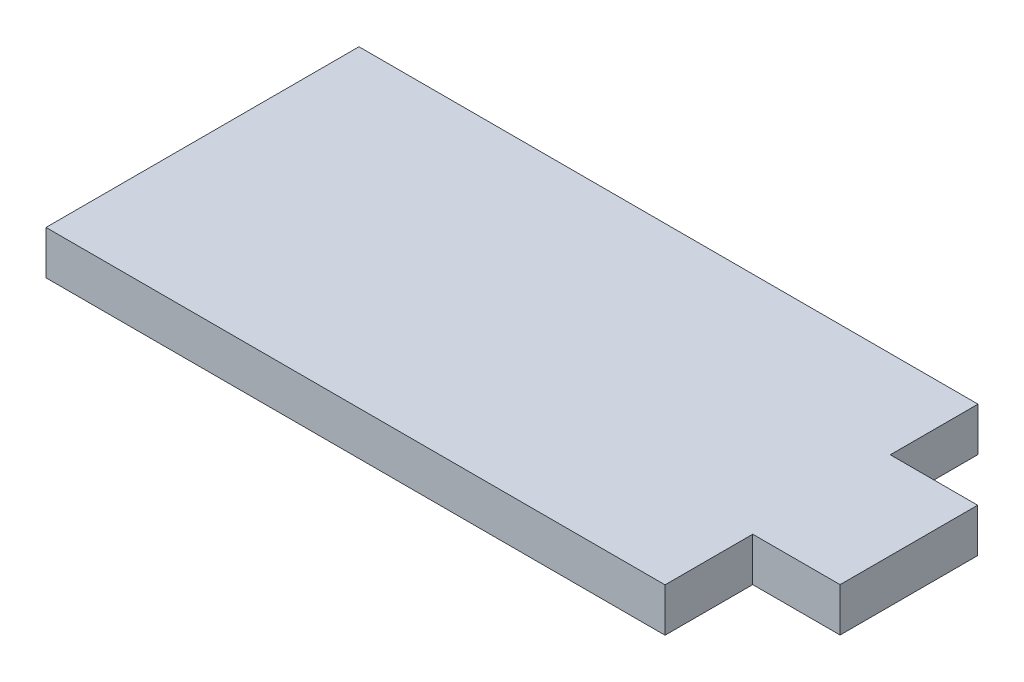
SolidWorks part; units mm, degrees
ref_plane "Front Plane" through (0, 0, 0) normal (0, 0, 1) x (1, 0, 0)
ref_plane "Top Plane" through (0, 0, 0) normal (0, 1, 0) x (1, 0, 0)
ref_plane "Right Plane" through (0, 0, 0) normal (1, 0, 0) x (0, 0, -1)
sketch "Sketch1" plane through (0, 0, 0) normal (0, 1, 0) x (1, 0, 0)
  line L0 (-22.5, 6.375) -> (22.5, 6.375)
  line L1 (22.5, 6.375) -> (22.5, 0)
  line L2 (22.5, 0) -> (28.85, 0)
  line L3 (28.85, 0) -> (28.85, -10)
  line L4 (28.85, -10) -> (22.5, -10)
  line L5 (22.5, -10) -> (22.5, -16.375)
  line L6 (22.5, -16.375) -> (-22.5, -16.375)
  line L7 (-22.5, -16.375) -> (-22.5, -10)
  line L8 (-22.5, -10) -> (-28.85, -10)
  line L9 (-28.85, -10) -> (-28.85, 0)
  line L10 (-28.85, 0) -> (-22.5, 0)
  line L11 (-22.5, 0) -> (-22.5, 6.375)
  line L12 (-22.5, 0) -> (-22.5, -10) construction
  point P11 (0, 6.375)
  point P14 (-28.85, -5)
  dimension "D1" = 6.35
  dimension "D2" = 10
  dimension "D3" = 45
  dimension "D4" = 22.75
extrude "Boss-Extrude1" add sketch "Sketch1" along normal blind 3.175 contours L11 L12 L7 L6 L5 L4 L3 L2 L1 L0 region at (1.4995, 0, 5)
equation "\"length\" = 22.75mm"
equation "\"w_mach\"= 45mm"
equation "\"w_tab\"= 10mm"
equation "\"t_wood\" = 0.125in"
equation "\"t_side\"= 0.25in"
equation "\"D1@Sketch1\"=\"t_side\""
equation "\"D2@Sketch1\"=\"w_tab\""
equation "\"D3@Sketch1\"=\"w_mach\""
equation "\"D4@Sketch1\"=\"length\""
equation "\"D1@Boss-Extrude1\"=\"t_wood\""
